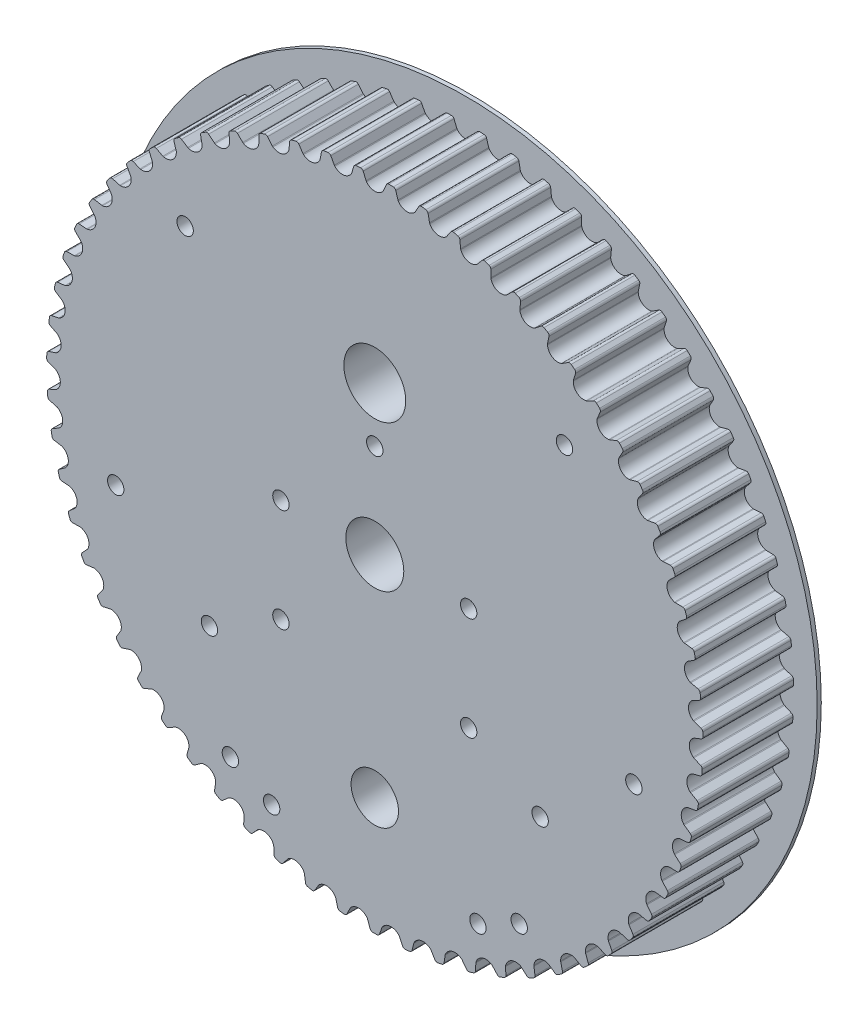
SolidWorks part; units mm, degrees
material "PETG"
ref_plane "Front Plane" through (0, 0, 0) normal (0, 0, 1) x (1, 0, 0)
ref_plane "Top Plane" through (0, 0, 0) normal (0, 1, 0) x (1, 0, 0)
ref_plane "Right Plane" through (0, 0, 0) normal (1, 0, 0) x (0, 0, -1)
sketch "Sketch1" plane through (0, 0, 0) normal (0, 0, 1) x (1, 0, 0)
  line L0 (0, 0) -> (0, 50000) construction
  line L1 (0, 0) -> (3.9983, 80.1144) construction
  line L2 (0, 0) -> (-3.9983, 80.1144) construction
  line L3 (-2.1085, 77.3973) -> (-2.8064, 79.0584)
  line L4 (2.1085, 77.3973) -> (2.8064, 79.0584)
  line L5 (5.6082, 77.2226) -> (5.0793, 78.9449)
  line L6 (9.8043, 76.8027) -> (10.6641, 78.3861)
  line L7 (13.2692, 76.2805) -> (12.9144, 78.0469)
  line L8 (17.4027, 75.4449) -> (18.4158, 76.9348)
  line L9 (20.7984, 74.5802) -> (20.6212, 76.3732)
  line L10 (24.8281, 73.3372) -> (25.9846, 74.7188)
  line L11 (28.1208, 72.1388) -> (28.123, 73.9405)
  line L12 (32.0068, 70.5007) -> (33.295, 71.7603)
  line L13 (35.1638, 68.9804) -> (35.3454, 70.7729)
  line L14 (38.8673, 66.9635) -> (40.2746, 68.0886)
  line L15 (41.8573, 65.1364) -> (42.2164, 66.902)
  line L16 (45.3416, 62.7608) -> (46.8539, 63.7402)
  line L17 (48.1348, 60.6451) -> (48.6679, 62.3661)
  line L18 (51.3652, 57.9344) -> (52.9675, 58.7583)
  line L19 (53.9339, 55.551) -> (54.6358, 57.2105)
  line L20 (56.8784, 52.5322) -> (58.5548, 53.1925)
  line L21 (59.197, 49.9049) -> (60.0606, 51.4862)
  line L22 (61.8263, 46.6079) -> (63.5601, 47.098)
  line L23 (63.8717, 43.7628) -> (64.8885, 45.2502)
  line L24 (66.1597, 40.2204) -> (67.9337, 40.5354)
  line L25 (67.9117, 37.1858) -> (69.0715, 38.5646)
  line L26 (69.8356, 33.4331) -> (71.6321, 33.57)
  line L27 (71.2767, 30.2392) -> (72.5681, 31.4956)
  line L28 (72.8174, 26.3136) -> (74.6186, 26.2709)
  line L29 (73.9334, 22.992) -> (75.3434, 24.1137)
  line L30 (75.0756, 18.9326) -> (76.8636, 18.7107)
  line L31 (75.8553, 15.5164) -> (77.37, 16.4921)
  line L32 (76.5876, 11.3634) -> (78.3446, 10.9646)
  line L33 (77.0233, 7.8865) -> (78.6276, 8.7066)
  line L34 (77.3384, 3.6813) -> (79.047, 3.1095)
  line L35 (77.4258, 0.1783) -> (79.1038, 0.8345)
  line L36 (77.3206, -4.0374) -> (78.9638, -4.7765)
  line L37 (77.0588, -7.5317) -> (78.7938, -7.0458)
  line L38 (76.5344, -11.716) -> (78.0959, -12.615)
  line L39 (75.9259, -15.1668) -> (77.7007, -14.8561)
  line L40 (74.9876, -19.2782) -> (76.4517, -20.3281)
  line L41 (74.0385, -22.6513) -> (75.8354, -22.5188)
  line L42 (72.6954, -26.6487) -> (74.0478, -27.8393)
  line L43 (71.4153, -29.9106) -> (73.2164, -29.9577)
  line L44 (69.6808, -33.7544) -> (70.908, -35.0737)
  line L45 (68.0823, -36.8726) -> (69.8697, -37.0988)
  line L46 (65.9737, -40.5247) -> (67.0634, -41.9596)
  line L47 (64.0726, -43.4682) -> (65.8287, -43.8712)
  line L48 (61.6109, -46.8922) -> (62.5523, -48.4284)
  line L49 (59.4262, -49.6317) -> (61.1334, -50.2076)
  line L50 (56.6358, -52.7936) -> (57.4196, -54.416)
  line L51 (54.1892, -55.302) -> (55.8306, -56.0451)
  line L52 (51.0978, -58.1704) -> (51.7161, -59.8627)
  line L53 (48.4136, -60.4227) -> (49.9728, -61.3255)
  line L54 (45.052, -62.969) -> (45.4988, -64.7145)
  line L55 (42.1568, -64.9429) -> (43.6185, -65.9965)
  line L56 (38.5585, -67.1418) -> (38.8292, -68.9231)
  line L57 (35.4811, -68.8177) -> (36.8306, -70.0115)
  line L58 (31.6817, -70.6474) -> (31.7737, -72.4468)
  line L59 (28.4528, -72.0085) -> (29.6767, -73.3307)
  line L60 (24.49, -73.4508) -> (24.4024, -75.2504)
  line L61 (21.1417, -74.4836) -> (22.2278, -75.9212)
  line L62 (17.055, -75.5242) -> (16.7887, -77.3062)
  line L63 (13.6204, -76.2185) -> (14.5581, -77.7571)
  line L64 (9.4505, -76.8471) -> (9.008, -78.5936)
  line L65 (5.9638, -77.1959) -> (6.7436, -78.8202)
  line L66 (1.752, -77.4061) -> (1.1379, -79.1)
  line L67 (-1.752, -77.4061) -> (-1.1379, -79.1)
  line L68 (-5.9638, -77.1959) -> (-6.7436, -78.8202)
  line L69 (-9.4505, -76.8471) -> (-9.008, -78.5936)
  line L70 (-13.6204, -76.2185) -> (-14.5581, -77.7571)
  line L71 (-17.055, -75.5242) -> (-16.7887, -77.3062)
  line L72 (-21.1417, -74.4836) -> (-22.2278, -75.9212)
  line L73 (-24.49, -73.4508) -> (-24.4024, -75.2504)
  line L74 (-28.4528, -72.0085) -> (-29.6767, -73.3307)
  line L75 (-31.6817, -70.6474) -> (-31.7737, -72.4468)
  line L76 (-35.4811, -68.8177) -> (-36.8306, -70.0115)
  line L77 (-38.5585, -67.1418) -> (-38.8292, -68.9231)
  line L78 (-42.1568, -64.9429) -> (-43.6185, -65.9965)
  line L79 (-45.052, -62.969) -> (-45.4988, -64.7145)
  line L80 (-48.4136, -60.4227) -> (-49.9728, -61.3255)
  line L81 (-51.0978, -58.1704) -> (-51.7161, -59.8627)
  line L82 (-54.1892, -55.302) -> (-55.8306, -56.0451)
  line L83 (-56.6358, -52.7936) -> (-57.4196, -54.416)
  line L84 (-59.4262, -49.6317) -> (-61.1334, -50.2076)
  line L85 (-61.6109, -46.8922) -> (-62.5523, -48.4284)
  line L86 (-64.0726, -43.4682) -> (-65.8287, -43.8712)
  line L87 (-65.9737, -40.5247) -> (-67.0634, -41.9596)
  line L88 (-68.0823, -36.8726) -> (-69.8697, -37.0988)
  line L89 (-69.6808, -33.7544) -> (-70.908, -35.0737)
  line L90 (-71.4153, -29.9106) -> (-73.2164, -29.9577)
  line L91 (-72.6954, -26.6487) -> (-74.0478, -27.8393)
  line L92 (-74.0385, -22.6513) -> (-75.8354, -22.5188)
  line L93 (-74.9876, -19.2782) -> (-76.4517, -20.3281)
  line L94 (-75.9259, -15.1668) -> (-77.7007, -14.8561)
  line L95 (-76.5344, -11.716) -> (-78.0959, -12.615)
  line L96 (-77.0588, -7.5317) -> (-78.7938, -7.0458)
  line L97 (-77.3206, -4.0374) -> (-78.9638, -4.7765)
  line L98 (-77.4258, 0.1783) -> (-79.1038, 0.8345)
  line L99 (-77.3384, 3.6813) -> (-79.047, 3.1095)
  line L100 (-77.0233, 7.8865) -> (-78.6276, 8.7066)
  line L101 (-76.5876, 11.3634) -> (-78.3446, 10.9646)
  line L102 (-75.8553, 15.5164) -> (-77.37, 16.4921)
  line L103 (-75.0756, 18.9326) -> (-76.8636, 18.7107)
  line L104 (-73.9334, 22.992) -> (-75.3434, 24.1137)
  line L105 (-72.8174, 26.3136) -> (-74.6186, 26.2709)
  line L106 (-71.2767, 30.2392) -> (-72.5681, 31.4956)
  line L107 (-69.8356, 33.4331) -> (-71.6321, 33.57)
  line L108 (-67.9117, 37.1858) -> (-69.0715, 38.5646)
  line L109 (-66.1597, 40.2204) -> (-67.9337, 40.5354)
  line L110 (-63.8717, 43.7628) -> (-64.8885, 45.2502)
  line L111 (-61.8263, 46.6079) -> (-63.5601, 47.098)
  line L112 (-59.197, 49.9049) -> (-60.0606, 51.4862)
  line L113 (-56.8784, 52.5322) -> (-58.5548, 53.1925)
  line L114 (-53.9339, 55.551) -> (-54.6358, 57.2105)
  line L115 (-51.3652, 57.9344) -> (-52.9675, 58.7583)
  line L116 (-48.1348, 60.6451) -> (-48.6679, 62.3661)
  line L117 (-45.3416, 62.7608) -> (-46.8539, 63.7402)
  line L118 (-41.8573, 65.1364) -> (-42.2164, 66.902)
  line L119 (-38.8673, 66.9635) -> (-40.2746, 68.0886)
  line L120 (-35.1638, 68.9804) -> (-35.3454, 70.7729)
  line L121 (-32.0068, 70.5007) -> (-33.295, 71.7603)
  line L122 (-28.1208, 72.1388) -> (-28.123, 73.9405)
  line L123 (0, 0) -> (2.0086, 77.226) construction
  line L124 (-24.8281, 73.3372) -> (-25.9846, 74.7188)
  line L125 (-20.7984, 74.5802) -> (-20.6212, 76.3732)
  line L126 (-17.4027, 75.4449) -> (-18.4158, 76.9348)
  line L127 (-13.2692, 76.2805) -> (-12.9144, 78.0469)
  line L128 (-9.8043, 76.8027) -> (-10.6641, 78.3861)
  line L129 (-5.6082, 77.2226) -> (-5.0793, 78.9449)
  circle A0 centre (0, 0) radius 80.2141 construction
  circle A317 centre (0, 0) radius 79.53 construction
  arc A318 (-2.0086, 77.226) -> (2.0086, 77.226) centre (0, 78.7807) ccw
  arc A319 (-2.0086, 77.226) -> (-2.1085, 77.3973) centre (-1.406, 77.6924) cw
  arc A320 (-2.8064, 79.0584) -> (-3.4334, 79.4559) centre (-3.4054, 78.8067) ccw
  arc A321 (-3.4334, 79.4559) -> (-3.9642, 79.4311) centre (0, 0) ccw
  arc A322 (3.4334, 79.4559) -> (3.9642, 79.4311) centre (0, 0) cw
  arc A323 (2.8064, 79.0584) -> (3.4334, 79.4559) centre (3.4054, 78.8067) cw
  arc A324 (2.0086, 77.226) -> (2.1085, 77.3973) centre (1.406, 77.6924) ccw
  arc A325 (4.4949, 79.4029) -> (3.9642, 79.4311) centre (0, 0) ccw
  arc A326 (5.0793, 78.9449) -> (4.4949, 79.4029) centre (4.4582, 78.7542) ccw
  arc A327 (5.6906, 77.0422) -> (9.6878, 76.6422) centre (7.844, 78.3892) ccw
  arc A328 (5.6906, 77.0422) -> (5.6082, 77.2226) centre (6.3366, 77.4463) cw
  arc A329 (9.6878, 76.6422) -> (9.8043, 76.8027) centre (9.1347, 77.1663) ccw
  arc A330 (10.6641, 78.3861) -> (11.3276, 78.7192) centre (11.2351, 78.0761) cw
  arc A331 (11.3276, 78.7192) -> (11.8533, 78.6417) centre (0, 0) cw
  arc A332 (12.3785, 78.5608) -> (11.8533, 78.6417) centre (0, 0) ccw
  arc A333 (12.9144, 78.0469) -> (12.3785, 78.5608) centre (12.2774, 77.919) ccw
  arc A334 (13.3333, 76.0928) -> (17.2708, 75.2968) centre (15.6101, 77.2187) ccw
  arc A335 (13.3333, 76.0928) -> (13.2692, 76.2805) centre (14.0163, 76.4305) cw
  arc A336 (17.2708, 75.2968) -> (17.4027, 75.4449) centre (16.7726, 75.8733) ccw
  arc A337 (18.4158, 76.9348) -> (19.1092, 77.2001) centre (18.9531, 76.5694) cw
  arc A338 (19.1092, 77.2001) -> (19.6246, 77.0707) centre (0, 0) cw
  arc A339 (20.1391, 76.9379) -> (19.6246, 77.0707) centre (0, 0) ccw
  arc A340 (20.6212, 76.3732) -> (20.1391, 76.9379) centre (19.9746, 76.3093) ccw
  arc A341 (20.8434, 74.3871) -> (24.6821, 73.203) centre (23.221, 75.2807) ccw
  arc A342 (20.8434, 74.3871) -> (20.7984, 74.5802) centre (21.5567, 74.6552) cw
  arc A343 (24.6821, 73.203) -> (24.8281, 73.3372) centre (24.2438, 73.8263) ccw
  arc A344 (25.9846, 74.7188) -> (26.7009, 74.9138) centre (26.4828, 74.3018) cw
  arc A345 (26.7009, 74.9138) -> (27.2009, 74.7338) centre (0, 0) cw
  arc A346 (27.6996, 74.5503) -> (27.2009, 74.7338) centre (0, 0) ccw
  arc A347 (28.123, 73.9405) -> (27.6996, 74.5503) centre (27.4733, 73.9413) ccw
  arc A348 (28.1464, 71.9421) -> (31.8481, 70.3817) centre (30.6012, 72.5945) ccw
  arc A349 (28.1464, 71.9421) -> (28.1208, 72.1388) centre (28.8828, 72.1378) cw
  arc A350 (31.8481, 70.3817) -> (32.0068, 70.5007) centre (31.474, 71.0455) ccw
  arc A351 (33.295, 71.7603) -> (34.0272, 71.883) centre (33.7493, 71.2958) cw
  arc A352 (34.0272, 71.883) -> (34.5068, 71.6541) centre (0, 0) cw
  arc A353 (34.9848, 71.4219) -> (34.5068, 71.6541) centre (0, 0) ccw
  arc A354 (35.3454, 70.7729) -> (34.9848, 71.4219) centre (34.699, 70.8384) ccw
  arc A355 (35.1696, 68.7821) -> (38.6976, 66.8609) centre (37.6772, 69.1869) ccw
  arc A356 (35.1696, 68.7821) -> (35.1638, 68.9804) centre (35.9219, 68.9036) cw
  arc A357 (38.6976, 66.8609) -> (38.8673, 66.9635) centre (38.3915, 67.5587) ccw
  arc A358 (40.2746, 68.0886) -> (41.0154, 68.1378) centre (40.6803, 67.5811) cw
  arc A359 (41.0154, 68.1378) -> (41.4697, 67.8622) centre (0, 0) cw
  arc A360 (41.9222, 67.5836) -> (41.4697, 67.8622) centre (0, 0) ccw
  arc A361 (42.2164, 66.902) -> (41.9222, 67.5836) centre (41.5798, 67.0315) ccw
  arc A362 (41.8434, 64.9386) -> (45.1625, 62.6756) centre (44.3787, 65.0917) ccw
  arc A363 (41.8434, 64.9386) -> (41.8573, 65.1364) centre (42.604, 64.9845) cw
  arc A364 (45.1625, 62.6756) -> (45.3416, 62.7608) centre (44.9274, 63.4004) ccw
  arc A365 (46.8539, 63.7402) -> (47.5959, 63.7154) centre (47.2071, 63.1949) cw
  arc A366 (47.5959, 63.7154) -> (48.0206, 63.3959) centre (0, 0) cw
  arc A367 (48.4431, 63.0737) -> (48.0206, 63.3959) centre (0, 0) ccw
  arc A368 (48.6679, 62.3661) -> (48.4431, 63.0737) centre (48.0473, 62.5584) ccw
  arc A369 (48.1012, 60.4496) -> (51.1786, 57.8674) centre (50.6393, 60.3495) ccw
  arc A370 (48.1012, 60.4496) -> (48.1348, 60.6451) centre (48.8626, 60.4196) cw
  arc A371 (51.1786, 57.8674) -> (51.3652, 57.9344) centre (51.0168, 58.6121) ccw
  arc A372 (52.9675, 58.7583) -> (53.7034, 58.6597) centre (53.2647, 58.1805) cw
  arc A373 (53.7034, 58.6597) -> (54.0941, 58.2996) centre (0, 0) cw
  arc A374 (54.4825, 57.9369) -> (54.0941, 58.2996) centre (0, 0) ccw
  arc A375 (54.6358, 57.2105) -> (54.4825, 57.9369) centre (54.0374, 57.4636) ccw
  arc A376 (53.881, 55.3599) -> (56.686, 52.4841) centre (56.3965, 55.0076) ccw
  arc A377 (53.881, 55.3599) -> (53.9339, 55.551) centre (54.6357, 55.2542) cw
  arc A378 (56.686, 52.4841) -> (56.8784, 52.5322) centre (56.5991, 53.2412) ccw
  arc A379 (58.5548, 53.1925) -> (59.2772, 53.0211) centre (58.7929, 52.588) cw
  arc A380 (59.2772, 53.0211) -> (59.6301, 52.6239) centre (0, 0) cw
  arc A381 (59.9804, 52.2243) -> (59.6301, 52.6239) centre (0, 0) ccw
  arc A382 (60.0606, 51.4862) -> (59.9804, 52.2243) centre (59.4904, 51.7976) ccw
  arc A383 (59.1254, 49.72) -> (61.63, 46.5792) centre (61.5932, 49.119) ccw
  arc A384 (59.1254, 49.72) -> (59.197, 49.9049) centre (59.8657, 49.5397) cw
  arc A385 (61.63, 46.5792) -> (61.8263, 46.6079) centre (61.619, 47.3411) ccw
  arc A386 (63.5601, 47.098) -> (64.2618, 46.8555) centre (63.7368, 46.4728) cw
  arc A387 (64.2618, 46.8555) -> (64.5734, 46.4251) centre (0, 0) cw
  arc A388 (64.8822, 45.9926) -> (64.5734, 46.4251) centre (0, 0) ccw
  arc A389 (64.8885, 45.2502) -> (64.8822, 45.9926) centre (64.3521, 45.6169) ccw
  arc A390 (63.7821, 43.5859) -> (65.9616, 40.2114) centre (66.1778, 42.7422) ccw
  arc A391 (63.7821, 43.5859) -> (63.8717, 43.7628) centre (64.5008, 43.3328) cw
  arc A392 (65.9616, 40.2114) -> (66.1597, 40.2204) centre (66.0264, 40.9706) ccw
  arc A393 (67.9337, 40.5354) -> (68.6078, 40.2243) centre (68.0473, 39.8957) cw
  arc A394 (68.6078, 40.2243) -> (68.875, 39.765) centre (0, 0) cw
  arc A395 (69.1392, 39.3039) -> (68.875, 39.765) centre (0, 0) ccw
  arc A396 (69.0715, 38.5646) -> (69.1392, 39.3039) centre (68.5743, 38.9828) ccw
  arc A397 (67.8049, 37.0187) -> (69.6375, 33.4439) centre (70.1047, 35.9406) ccw
  arc A398 (67.8049, 37.0187) -> (67.9117, 37.1858) centre (68.4948, 36.6953) cw
  arc A399 (69.6375, 33.4439) -> (69.8356, 33.4331) centre (69.7777, 34.1929) ccw
  arc A400 (71.6321, 33.57) -> (72.2719, 33.1933) centre (71.6815, 32.9221) cw
  arc A401 (72.2719, 33.1933) -> (72.4921, 32.7097) centre (0, 0) cw
  arc A402 (72.709, 32.2246) -> (72.4921, 32.7097) centre (0, 0) ccw
  arc A403 (72.5681, 31.4956) -> (72.709, 32.2246) centre (72.115, 31.9613) ccw
  arc A404 (71.1538, 30.0836) -> (72.6214, 26.3441) centre (73.3349, 28.7818) ccw
  arc A405 (71.1538, 30.0836) -> (71.2767, 30.2392) centre (71.8081, 29.693) cw
  arc A406 (72.6214, 26.3441) -> (72.8174, 26.3136) centre (72.8355, 27.0754) ccw
  arc A407 (74.6186, 26.2709) -> (75.2177, 25.8324) centre (74.6032, 25.6214) cw
  arc A408 (75.2177, 25.8324) -> (75.3887, 25.3292) centre (0, 0) cw
  arc A409 (75.5562, 24.825) -> (75.3887, 25.3292) centre (0, 0) ccw
  arc A410 (75.3434, 24.1137) -> (75.5562, 24.825) centre (74.939, 24.6222) ccw
  arc A411 (73.7956, 22.8494) -> (74.8836, 18.9824) centre (75.8362, 21.337) ccw
  arc A412 (73.7956, 22.8494) -> (73.9334, 22.992) centre (74.4078, 22.3957) cw
  arc A413 (74.8836, 18.9824) -> (75.0756, 18.9326) centre (75.1694, 19.6888) ccw
  arc A414 (76.8636, 18.7107) -> (77.416, 18.2148) centre (76.7836, 18.066) cw
  arc A415 (77.416, 18.2148) -> (77.536, 17.6971) centre (0, 0) cw
  arc A416 (77.6525, 17.1786) -> (77.536, 17.6971) centre (0, 0) ccw
  arc A417 (77.37, 16.4921) -> (77.6525, 17.1786) centre (77.0181, 17.0383) ccw
  arc A418 (75.7039, 15.3882) -> (76.4015, 11.4321) centre (77.5838, 13.6801) ccw
  arc A419 (75.7039, 15.3882) -> (75.8553, 15.5164) centre (76.2679, 14.8758) cw
  arc A420 (76.4015, 11.4321) -> (76.5876, 11.3634) centre (76.7562, 12.1065) ccw
  arc A421 (78.3446, 10.9646) -> (78.8449, 10.4161) centre (78.2008, 10.331) cw
  arc A422 (78.8449, 10.4161) -> (78.9128, 9.8891) centre (0, 0) cw
  arc A423 (78.9771, 9.3616) -> (78.9128, 9.8891) centre (0, 0) ccw
  arc A424 (78.6276, 8.7066) -> (78.9771, 9.3616) centre (78.3319, 9.2851) ccw
  arc A425 (76.8599, 7.7741) -> (77.1601, 3.7681) centre (78.5604, 5.8873) ccw
  arc A426 (76.8599, 7.7741) -> (77.0233, 7.8865) centre (77.3701, 7.208) cw
  arc A427 (77.1601, 3.7681) -> (77.3384, 3.6813) centre (77.5802, 4.4039) ccw
  arc A428 (79.047, 3.1095) -> (79.4903, 2.5139) centre (78.8409, 2.4934) cw
  arc A429 (79.4903, 2.5139) -> (79.5053, 1.9827) centre (0, 0) cw
  arc A430 (79.5168, 1.4515) -> (79.5053, 1.9827) centre (0, 0) ccw
  arc A431 (79.1038, 0.8345) -> (79.5168, 1.4515) centre (78.8671, 1.4396) ccw
  arc A432 (77.252, 0.0827) -> (77.1519, -3.9333) centre (78.7562, -1.9641) ccw
  arc A433 (77.252, 0.0827) -> (77.4258, 0.1783) centre (77.7033, -0.5314) cw
  arc A434 (77.1519, -3.9333) -> (77.3206, -4.0374) centre (77.6332, -3.3425) ccw
  arc A435 (78.9638, -4.7765) -> (79.3456, -5.4133) centre (78.6973, -5.369) cw
  arc A436 (79.3456, -5.4133) -> (79.3076, -5.9433) centre (0, 0) cw
  arc A437 (79.2661, -6.4731) -> (79.3076, -5.9433) centre (0, 0) ccw
  arc A438 (78.7938, -7.0458) -> (79.2661, -6.4731) centre (78.6186, -6.4202) ccw
  arc A439 (76.8764, -7.6096) -> (76.3769, -11.5956) centre (78.1693, -9.7959) ccw
  arc A440 (76.8764, -7.6096) -> (77.0588, -7.5317) centre (77.2643, -8.2655) cw
  arc A441 (76.3769, -11.5956) -> (76.5344, -11.716) centre (76.9146, -11.0557) ccw
  arc A442 (78.0959, -12.615) -> (78.4123, -13.2866) centre (77.7717, -13.1781) cw
  arc A443 (78.4123, -13.2866) -> (78.3218, -13.8102) centre (0, 0) cw
  arc A444 (78.2277, -14.3332) -> (78.3218, -13.8102) centre (0, 0) ccw
  arc A445 (77.7007, -14.8561) -> (78.2277, -14.3332) centre (77.5887, -14.2161) ccw
  arc A446 (75.7367, -15.2262) -> (74.8428, -19.1426) centre (76.8055, -17.5304) ccw
  arc A447 (75.7367, -15.2262) -> (75.9259, -15.1668) centre (76.0573, -15.9174) cw
  arc A448 (74.8428, -19.1426) -> (74.9876, -19.2782) centre (75.4316, -18.6589) ccw
  arc A449 (76.4517, -20.3281) -> (76.6997, -21.0279) centre (76.0731, -20.8561) cw
  arc A450 (76.6997, -21.0279) -> (76.5575, -21.5399) centre (0, 0) cw
  arc A451 (76.4119, -22.051) -> (76.5575, -21.5399) centre (0, 0) ccw
  arc A452 (75.8354, -22.5188) -> (76.4119, -22.051) centre (75.7876, -21.8708) ccw
  arc A453 (73.8443, -22.6914) -> (72.5649, -26.4994) centre (74.6784, -25.0906) ccw
  arc A454 (73.8443, -22.6914) -> (74.0385, -22.6513) centre (74.0945, -23.4112) cw
  arc A455 (72.5649, -26.4994) -> (72.6954, -26.6487) centre (73.1989, -26.0768) ccw
  arc A456 (74.0478, -27.8393) -> (74.2249, -28.5603) centre (73.6185, -28.3269) cw
  arc A457 (74.2249, -28.5603) -> (74.0324, -29.0556) centre (0, 0) cw
  arc A458 (73.8366, -29.5496) -> (74.0324, -29.0556) centre (0, 0) ccw
  arc A459 (73.2164, -29.9577) -> (73.8366, -29.5496) centre (73.2334, -29.3082) ccw
  arc A460 (71.218, -29.9312) -> (69.5658, -33.5929) centre (71.8091, -32.4015) ccw
  arc A461 (71.218, -29.9312) -> (71.4153, -29.9106) centre (71.3953, -30.6723) cw
  arc A462 (69.5658, -33.5929) -> (69.6808, -33.7544) centre (70.2388, -33.2355) ccw
  arc A463 (70.908, -35.0737) -> (71.0123, -35.8088) centre (70.4322, -35.5162) cw
  arc A464 (71.0123, -35.8088) -> (70.7715, -36.2824) centre (0, 0) cw
  arc A465 (70.5275, -36.7545) -> (70.7715, -36.2824) centre (0, 0) ccw
  arc A466 (69.8697, -37.0988) -> (70.5275, -36.7545) centre (69.9513, -36.4542) ccw
  arc A467 (67.8839, -36.8735) -> (65.8754, -40.3525) centre (68.2261, -39.3903) ccw
  arc A468 (67.8839, -36.8735) -> (68.0823, -36.8726) centre (67.9866, -37.6286) cw
  arc A469 (65.8754, -40.3525) -> (65.9737, -40.5247) centre (66.5806, -40.0638) ccw
  arc A470 (67.0634, -41.9596) -> (67.0941, -42.7014) centre (66.5459, -42.3525) cw
  arc A471 (67.0941, -42.7014) -> (66.8073, -43.1487) centre (0, 0) cw
  arc A472 (66.5175, -43.5941) -> (66.8073, -43.1487) centre (0, 0) ccw
  arc A473 (65.8287, -43.8712) -> (66.5175, -43.5941) centre (65.974, -43.238) ccw
  arc A474 (63.8752, -43.4493) -> (61.5302, -46.711) centre (63.965, -45.9877) ccw
  arc A475 (63.8752, -43.4493) -> (64.0726, -43.4682) centre (63.9021, -44.2108) cw
  arc A476 (61.5302, -46.711) -> (61.6109, -46.8922) centre (62.2607, -46.494) ccw
  arc A477 (62.5523, -48.4284) -> (62.509, -49.1696) centre (61.9983, -48.7679) cw
  arc A478 (62.509, -49.1696) -> (62.1791, -49.5861) centre (0, 0) cw
  arc A479 (61.8464, -50.0005) -> (62.1791, -49.5861) centre (0, 0) ccw
  arc A480 (61.1334, -50.2076) -> (61.8464, -50.0005) centre (61.3411, -49.592) ccw
  arc A481 (59.2316, -49.5933) -> (56.5735, -52.6053) centre (59.0683, -52.1281) ccw
  arc A482 (59.2316, -49.5933) -> (59.4262, -49.6317) centre (59.1826, -50.3538) cw
  arc A483 (56.5735, -52.6053) -> (56.6358, -52.7936) centre (57.322, -52.4621) ccw
  arc A484 (57.4196, -54.416) -> (57.3027, -55.1491) centre (56.8345, -54.6986) cw
  arc A485 (57.3027, -55.1491) -> (56.9329, -55.5308) centre (0, 0) cw
  arc A486 (56.5606, -55.9099) -> (56.9329, -55.5308) centre (0, 0) ccw
  arc A487 (55.8306, -56.0451) -> (56.5606, -55.9099) centre (56.0985, -55.4532) ccw
  arc A488 (53.9994, -55.2445) -> (51.0546, -57.9768) centre (53.5845, -57.7503) ccw
  arc A489 (53.9994, -55.2445) -> (54.1892, -55.302) centre (53.8749, -55.9962) cw
  arc A490 (51.0546, -57.9768) -> (51.0978, -58.1704) centre (51.8136, -57.9089) ccw
  arc A491 (51.7161, -59.8627) -> (51.5268, -60.5806) centre (51.1059, -60.0857) cw
  arc A492 (51.5268, -60.5806) -> (51.1209, -60.9235) centre (0, 0) cw
  arc A493 (50.7127, -61.2637) -> (51.1209, -60.9235) centre (0, 0) ccw
  arc A494 (49.9728, -61.3255) -> (50.7127, -61.2637) centre (50.2984, -60.7632) ccw
  arc A495 (48.2305, -60.3465) -> (45.0283, -62.7721) centre (47.5681, -62.7987) ccw
  arc A496 (48.2305, -60.3465) -> (48.4136, -60.4227) centre (48.0318, -61.0822) cw
  arc A497 (45.0283, -62.7721) -> (45.052, -62.969) centre (45.7902, -62.7801) ccw
  arc A498 (45.4988, -64.7145) -> (45.2389, -65.41) centre (44.8693, -64.8756) cw
  arc A499 (45.2389, -65.41) -> (44.8008, -65.7108) centre (0, 0) cw
  arc A500 (44.3608, -66.0086) -> (44.8008, -65.7108) centre (0, 0) ccw
  arc A501 (43.6185, -65.9965) -> (44.3608, -66.0086) centre (43.9984, -65.4694) ccw
  arc A502 (41.9822, -64.8489) -> (38.5544, -66.9436) centre (41.079, -67.2229) ccw
  arc A503 (41.9822, -64.8489) -> (42.1568, -64.9429) centre (41.7113, -65.5611) cw
  arc A504 (38.5544, -66.9436) -> (38.5585, -67.1418) centre (39.3118, -67.0273) ccw
  arc A505 (38.8292, -68.9231) -> (38.5014, -69.5893) centre (38.1868, -69.0208) cw
  arc A506 (38.5014, -69.5893) -> (38.0355, -69.845) centre (0, 0) cw
  arc A507 (37.568, -70.0975) -> (38.0355, -69.845) centre (0, 0) ccw
  arc A508 (36.8306, -70.0115) -> (37.568, -70.0975) centre (37.2611, -69.5249) ccw
  arc A509 (35.3168, -68.7067) -> (31.6974, -70.4497) centre (34.1817, -70.979) ccw
  arc A510 (35.3168, -68.7067) -> (35.4811, -68.8177) centre (34.9762, -69.3884) cw
  arc A511 (31.6974, -70.4497) -> (31.6817, -70.6474) centre (32.4427, -70.6085) ccw
  arc A512 (31.7737, -72.4468) -> (31.3812, -73.077) centre (31.1248, -72.48) cw
  arc A513 (31.3812, -73.077) -> (30.8922, -73.285) centre (0, 0) cw
  arc A514 (30.4019, -73.4898) -> (30.8922, -73.285) centre (0, 0) ccw
  arc A515 (29.6767, -73.3307) -> (30.4019, -73.4898) centre (30.1535, -72.8894) ccw
  arc A516 (28.3003, -71.8817) -> (24.5254, -73.2556) centre (26.9446, -74.0296) ccw
  arc A517 (28.3003, -71.8817) -> (28.4528, -72.0085) centre (27.8936, -72.5261) cw
  arc A518 (24.5254, -73.2556) -> (24.49, -73.4508) centre (25.2511, -73.4878) ccw
  arc A519 (24.4024, -75.2504) -> (23.9491, -75.8384) centre (23.7535, -75.2188) cw
  arc A520 (23.9491, -75.8384) -> (23.4419, -75.9967) centre (0, 0) cw
  arc A521 (22.9336, -76.1516) -> (23.4419, -75.9967) centre (0, 0) ccw
  arc A522 (22.2278, -75.9212) -> (22.9336, -76.1516) centre (22.7462, -75.5295) ccw
  arc A523 (21.0026, -74.3423) -> (17.1096, -75.3336) centre (19.4397, -76.3446) ccw
  arc A524 (21.0026, -74.3423) -> (21.1417, -74.4836) centre (20.5337, -74.943) cw
  arc A525 (17.1096, -75.3336) -> (17.055, -75.5242) centre (17.8086, -75.6369) ccw
  arc A526 (16.7887, -77.3062) -> (16.2791, -77.8461) centre (16.1461, -77.2101) cw
  arc A527 (16.2791, -77.8461) -> (15.7586, -77.9531) centre (0, 0) cw
  arc A528 (15.2374, -78.0567) -> (15.7586, -77.9531) centre (0, 0) ccw
  arc A529 (14.5581, -77.7571) -> (15.2374, -78.0567) centre (15.1129, -77.419) ccw
  arc A530 (13.4961, -76.0641) -> (9.5238, -76.6628) centre (11.7417, -77.9008) ccw
  arc A531 (13.4961, -76.0641) -> (13.6204, -76.2185) centre (12.9698, -76.6151) cw
  arc A532 (9.5238, -76.6628) -> (9.4505, -76.8471) centre (10.1891, -77.0342) ccw
  arc A533 (9.008, -78.5936) -> (8.4472, -79.0801) centre (8.3782, -78.4341) cw
  arc A534 (8.4472, -79.0801) -> (7.9186, -79.1348) centre (0, 0) cw
  arc A535 (7.3897, -79.1859) -> (7.9186, -79.1348) centre (0, 0) ccw
  arc A536 (6.7436, -78.8202) -> (7.3897, -79.1859) centre (7.3293, -78.539) ccw
  arc A537 (5.8555, -77.0298) -> (1.8433, -77.2301) centre (3.9269, -78.6828) ccw
  arc A538 (5.8555, -77.0298) -> (5.9638, -77.1959) centre (5.2769, -77.5257) cw
  arc A539 (1.8433, -77.2301) -> (1.752, -77.4061) centre (2.4684, -77.6659) ccw
  arc A540 (1.1379, -79.1) -> (0.5314, -79.5282) centre (0.527, -78.8785) cw
  arc A541 (0.5314, -79.5282) -> (0, -79.53) centre (0, 0) cw
  arc A542 (-0.5314, -79.5282) -> (0, -79.53) centre (0, 0) ccw
  arc A543 (-1.1379, -79.1) -> (-0.5314, -79.5282) centre (-0.527, -78.8785) ccw
  arc A544 (-1.8433, -77.2301) -> (-5.8555, -77.0298) centre (-3.9269, -78.6828) ccw
  arc A545 (-1.8433, -77.2301) -> (-1.752, -77.4061) centre (-2.4684, -77.6659) cw
  arc A546 (-5.8555, -77.0298) -> (-5.9638, -77.1959) centre (-5.2769, -77.5257) ccw
  arc A547 (-6.7436, -78.8202) -> (-7.3897, -79.1859) centre (-7.3293, -78.539) cw
  arc A548 (-7.3897, -79.1859) -> (-7.9186, -79.1348) centre (0, 0) cw
  arc A549 (-8.4472, -79.0801) -> (-7.9186, -79.1348) centre (0, 0) ccw
  arc A550 (-9.008, -78.5936) -> (-8.4472, -79.0801) centre (-8.3782, -78.4341) ccw
  arc A551 (-9.5238, -76.6628) -> (-13.4961, -76.0641) centre (-11.7417, -77.9008) ccw
  arc A552 (-9.5238, -76.6628) -> (-9.4505, -76.8471) centre (-10.1891, -77.0342) cw
  arc A553 (-13.4961, -76.0641) -> (-13.6204, -76.2185) centre (-12.9698, -76.6151) ccw
  arc A554 (-14.5581, -77.7571) -> (-15.2374, -78.0567) centre (-15.1129, -77.419) cw
  arc A555 (-15.2374, -78.0567) -> (-15.7586, -77.9531) centre (0, 0) cw
  arc A556 (-16.2791, -77.8461) -> (-15.7586, -77.9531) centre (0, 0) ccw
  arc A557 (-16.7887, -77.3062) -> (-16.2791, -77.8461) centre (-16.1461, -77.2101) ccw
  arc A558 (-17.1096, -75.3336) -> (-21.0026, -74.3423) centre (-19.4397, -76.3446) ccw
  arc A559 (-17.1096, -75.3336) -> (-17.055, -75.5242) centre (-17.8086, -75.6369) cw
  arc A560 (-21.0026, -74.3423) -> (-21.1417, -74.4836) centre (-20.5337, -74.943) ccw
  arc A561 (-22.2278, -75.9212) -> (-22.9336, -76.1516) centre (-22.7462, -75.5295) cw
  arc A562 (-22.9336, -76.1516) -> (-23.4419, -75.9967) centre (0, 0) cw
  arc A563 (-23.9491, -75.8384) -> (-23.4419, -75.9967) centre (0, 0) ccw
  arc A564 (-24.4024, -75.2504) -> (-23.9491, -75.8384) centre (-23.7535, -75.2188) ccw
  arc A565 (-24.5254, -73.2556) -> (-28.3003, -71.8817) centre (-26.9446, -74.0296) ccw
  arc A566 (-24.5254, -73.2556) -> (-24.49, -73.4508) centre (-25.2511, -73.4878) cw
  arc A567 (-28.3003, -71.8817) -> (-28.4528, -72.0085) centre (-27.8936, -72.5261) ccw
  arc A568 (-29.6767, -73.3307) -> (-30.4019, -73.4898) centre (-30.1535, -72.8894) cw
  arc A569 (-30.4019, -73.4898) -> (-30.8922, -73.285) centre (0, 0) cw
  arc A570 (-31.3812, -73.077) -> (-30.8922, -73.285) centre (0, 0) ccw
  arc A571 (-31.7737, -72.4468) -> (-31.3812, -73.077) centre (-31.1248, -72.48) ccw
  arc A572 (-31.6974, -70.4497) -> (-35.3168, -68.7067) centre (-34.1817, -70.979) ccw
  arc A573 (-31.6974, -70.4497) -> (-31.6817, -70.6474) centre (-32.4427, -70.6085) cw
  arc A574 (-35.3168, -68.7067) -> (-35.4811, -68.8177) centre (-34.9762, -69.3884) ccw
  arc A575 (-36.8306, -70.0115) -> (-37.568, -70.0975) centre (-37.2611, -69.5249) cw
  arc A576 (-37.568, -70.0975) -> (-38.0355, -69.845) centre (0, 0) cw
  arc A577 (-38.5014, -69.5893) -> (-38.0355, -69.845) centre (0, 0) ccw
  arc A578 (-38.8292, -68.9231) -> (-38.5014, -69.5893) centre (-38.1868, -69.0208) ccw
  arc A579 (-38.5544, -66.9436) -> (-41.9822, -64.8489) centre (-41.079, -67.2229) ccw
  arc A580 (-38.5544, -66.9436) -> (-38.5585, -67.1418) centre (-39.3118, -67.0273) cw
  arc A581 (-41.9822, -64.8489) -> (-42.1568, -64.9429) centre (-41.7113, -65.5611) ccw
  arc A582 (-43.6185, -65.9965) -> (-44.3608, -66.0086) centre (-43.9984, -65.4694) cw
  arc A583 (-44.3608, -66.0086) -> (-44.8008, -65.7108) centre (0, 0) cw
  arc A584 (-45.2389, -65.41) -> (-44.8008, -65.7108) centre (0, 0) ccw
  arc A585 (-45.4988, -64.7145) -> (-45.2389, -65.41) centre (-44.8693, -64.8756) ccw
  arc A586 (-45.0283, -62.7721) -> (-48.2305, -60.3465) centre (-47.5681, -62.7987) ccw
  arc A587 (-45.0283, -62.7721) -> (-45.052, -62.969) centre (-45.7902, -62.7801) cw
  arc A588 (-48.2305, -60.3465) -> (-48.4136, -60.4227) centre (-48.0318, -61.0822) ccw
  arc A589 (-49.9728, -61.3255) -> (-50.7127, -61.2637) centre (-50.2984, -60.7632) cw
  arc A590 (-50.7127, -61.2637) -> (-51.1209, -60.9235) centre (0, 0) cw
  arc A591 (-51.5268, -60.5806) -> (-51.1209, -60.9235) centre (0, 0) ccw
  arc A592 (-51.7161, -59.8627) -> (-51.5268, -60.5806) centre (-51.1059, -60.0857) ccw
  arc A593 (-51.0546, -57.9768) -> (-53.9994, -55.2445) centre (-53.5845, -57.7503) ccw
  arc A594 (-51.0546, -57.9768) -> (-51.0978, -58.1704) centre (-51.8136, -57.9089) cw
  arc A595 (-53.9994, -55.2445) -> (-54.1892, -55.302) centre (-53.8749, -55.9962) ccw
  arc A596 (-55.8306, -56.0451) -> (-56.5606, -55.9099) centre (-56.0985, -55.4532) cw
  arc A597 (-56.5606, -55.9099) -> (-56.9329, -55.5308) centre (0, 0) cw
  arc A598 (-57.3027, -55.1491) -> (-56.9329, -55.5308) centre (0, 0) ccw
  arc A599 (-57.4196, -54.416) -> (-57.3027, -55.1491) centre (-56.8345, -54.6986) ccw
  arc A600 (-56.5735, -52.6053) -> (-59.2316, -49.5933) centre (-59.0683, -52.1281) ccw
  arc A601 (-56.5735, -52.6053) -> (-56.6358, -52.7936) centre (-57.322, -52.4621) cw
  arc A602 (-59.2316, -49.5933) -> (-59.4262, -49.6317) centre (-59.1826, -50.3538) ccw
  arc A603 (-61.1334, -50.2076) -> (-61.8464, -50.0005) centre (-61.3411, -49.592) cw
  arc A604 (-61.8464, -50.0005) -> (-62.1791, -49.5861) centre (0, 0) cw
  arc A605 (-62.509, -49.1696) -> (-62.1791, -49.5861) centre (0, 0) ccw
  arc A606 (-62.5523, -48.4284) -> (-62.509, -49.1696) centre (-61.9983, -48.7679) ccw
  arc A607 (-61.5302, -46.711) -> (-63.8752, -43.4493) centre (-63.965, -45.9877) ccw
  arc A608 (-61.5302, -46.711) -> (-61.6109, -46.8922) centre (-62.2607, -46.494) cw
  arc A609 (-63.8752, -43.4493) -> (-64.0726, -43.4682) centre (-63.9021, -44.2108) ccw
  arc A610 (-65.8287, -43.8712) -> (-66.5175, -43.5941) centre (-65.974, -43.238) cw
  arc A611 (-66.5175, -43.5941) -> (-66.8073, -43.1487) centre (0, 0) cw
  arc A612 (-67.0941, -42.7014) -> (-66.8073, -43.1487) centre (0, 0) ccw
  arc A613 (-67.0634, -41.9596) -> (-67.0941, -42.7014) centre (-66.5459, -42.3525) ccw
  arc A614 (-65.8754, -40.3525) -> (-67.8839, -36.8735) centre (-68.2261, -39.3904) ccw
  arc A615 (-65.8754, -40.3525) -> (-65.9737, -40.5247) centre (-66.5806, -40.0638) cw
  arc A616 (-67.8839, -36.8735) -> (-68.0823, -36.8726) centre (-67.9866, -37.6286) ccw
  arc A617 (-69.8697, -37.0988) -> (-70.5275, -36.7545) centre (-69.9513, -36.4542) cw
  arc A618 (-70.5275, -36.7545) -> (-70.7715, -36.2824) centre (0, 0) cw
  arc A619 (-71.0123, -35.8088) -> (-70.7715, -36.2824) centre (0, 0) ccw
  arc A620 (-70.908, -35.0737) -> (-71.0123, -35.8088) centre (-70.4322, -35.5162) ccw
  arc A621 (-69.5658, -33.5929) -> (-71.218, -29.9312) centre (-71.8091, -32.4015) ccw
  arc A622 (-69.5658, -33.5929) -> (-69.6808, -33.7544) centre (-70.2388, -33.2355) cw
  arc A623 (-71.218, -29.9312) -> (-71.4153, -29.9106) centre (-71.3953, -30.6723) ccw
  arc A624 (-73.2164, -29.9577) -> (-73.8366, -29.5496) centre (-73.2334, -29.3082) cw
  arc A625 (-73.8366, -29.5496) -> (-74.0324, -29.0556) centre (0, 0) cw
  arc A626 (-74.2249, -28.5603) -> (-74.0324, -29.0556) centre (0, 0) ccw
  arc A627 (-74.0478, -27.8393) -> (-74.2249, -28.5603) centre (-73.6185, -28.3269) ccw
  arc A628 (-72.5649, -26.4994) -> (-73.8443, -22.6914) centre (-74.6784, -25.0906) ccw
  arc A629 (-72.5649, -26.4994) -> (-72.6954, -26.6487) centre (-73.1989, -26.0768) cw
  arc A630 (-73.8443, -22.6914) -> (-74.0385, -22.6513) centre (-74.0945, -23.4112) ccw
  arc A631 (-75.8354, -22.5188) -> (-76.4119, -22.051) centre (-75.7876, -21.8708) cw
  arc A632 (-76.4119, -22.051) -> (-76.5575, -21.5399) centre (0, 0) cw
  arc A633 (-76.6997, -21.0279) -> (-76.5575, -21.5399) centre (0, 0) ccw
  arc A634 (-76.4517, -20.3281) -> (-76.6997, -21.0279) centre (-76.0731, -20.8561) ccw
  arc A635 (-74.8428, -19.1426) -> (-75.7367, -15.2262) centre (-76.8055, -17.5304) ccw
  arc A636 (-74.8428, -19.1426) -> (-74.9876, -19.2782) centre (-75.4316, -18.6589) cw
  arc A637 (-75.7367, -15.2262) -> (-75.9259, -15.1668) centre (-76.0573, -15.9174) ccw
  arc A638 (-77.7007, -14.8561) -> (-78.2277, -14.3332) centre (-77.5887, -14.2161) cw
  arc A639 (-78.2277, -14.3332) -> (-78.3218, -13.8102) centre (0, 0) cw
  arc A640 (-78.4123, -13.2866) -> (-78.3218, -13.8102) centre (0, 0) ccw
  arc A641 (-78.0959, -12.615) -> (-78.4123, -13.2866) centre (-77.7717, -13.1781) ccw
  arc A642 (-76.3769, -11.5956) -> (-76.8764, -7.6096) centre (-78.1693, -9.7959) ccw
  arc A643 (-76.3769, -11.5956) -> (-76.5344, -11.716) centre (-76.9146, -11.0557) cw
  arc A644 (-76.8764, -7.6096) -> (-77.0588, -7.5317) centre (-77.2643, -8.2655) ccw
  arc A645 (-78.7938, -7.0458) -> (-79.2661, -6.4731) centre (-78.6186, -6.4202) cw
  arc A646 (-79.2661, -6.4731) -> (-79.3076, -5.9433) centre (0, 0) cw
  arc A647 (-79.3456, -5.4133) -> (-79.3076, -5.9433) centre (0, 0) ccw
  arc A648 (-78.9638, -4.7765) -> (-79.3456, -5.4133) centre (-78.6973, -5.369) ccw
  arc A649 (-77.1519, -3.9333) -> (-77.252, 0.0827) centre (-78.7562, -1.9641) ccw
  arc A650 (-77.1519, -3.9333) -> (-77.3206, -4.0374) centre (-77.6332, -3.3425) cw
  arc A651 (-77.252, 0.0827) -> (-77.4258, 0.1783) centre (-77.7033, -0.5314) ccw
  arc A652 (-79.1038, 0.8345) -> (-79.5168, 1.4515) centre (-78.8671, 1.4396) cw
  arc A653 (-79.5168, 1.4515) -> (-79.5053, 1.9827) centre (0, 0) cw
  arc A654 (-79.4903, 2.5139) -> (-79.5053, 1.9827) centre (0, 0) ccw
  arc A655 (-79.047, 3.1095) -> (-79.4903, 2.5139) centre (-78.8409, 2.4934) ccw
  arc A656 (-77.1601, 3.7681) -> (-76.8599, 7.7741) centre (-78.5604, 5.8873) ccw
  arc A657 (-77.1601, 3.7681) -> (-77.3384, 3.6813) centre (-77.5802, 4.4039) cw
  arc A658 (-76.8599, 7.7741) -> (-77.0233, 7.8865) centre (-77.3701, 7.208) ccw
  arc A659 (-78.6276, 8.7066) -> (-78.9771, 9.3616) centre (-78.3319, 9.2851) cw
  arc A660 (-78.9771, 9.3616) -> (-78.9128, 9.8891) centre (0, 0) cw
  arc A661 (-78.8449, 10.4161) -> (-78.9128, 9.8891) centre (0, 0) ccw
  arc A662 (-78.3446, 10.9646) -> (-78.8449, 10.4161) centre (-78.2008, 10.331) ccw
  arc A663 (-76.4015, 11.4321) -> (-75.7039, 15.3882) centre (-77.5838, 13.6801) ccw
  arc A664 (-76.4015, 11.4321) -> (-76.5876, 11.3634) centre (-76.7562, 12.1065) cw
  arc A665 (-75.7039, 15.3882) -> (-75.8553, 15.5164) centre (-76.2679, 14.8758) ccw
  arc A666 (-77.37, 16.4921) -> (-77.6525, 17.1786) centre (-77.0181, 17.0383) cw
  arc A667 (-77.6525, 17.1786) -> (-77.536, 17.6971) centre (0, 0) cw
  arc A668 (-77.416, 18.2148) -> (-77.536, 17.6971) centre (0, 0) ccw
  arc A669 (-76.8636, 18.7107) -> (-77.416, 18.2148) centre (-76.7836, 18.066) ccw
  arc A670 (-74.8836, 18.9824) -> (-73.7956, 22.8494) centre (-75.8362, 21.337) ccw
  arc A671 (-74.8836, 18.9824) -> (-75.0756, 18.9326) centre (-75.1694, 19.6888) cw
  arc A672 (-73.7956, 22.8494) -> (-73.9334, 22.992) centre (-74.4078, 22.3957) ccw
  arc A673 (-75.3434, 24.1137) -> (-75.5562, 24.825) centre (-74.939, 24.6222) cw
  arc A674 (-75.5562, 24.825) -> (-75.3887, 25.3292) centre (0, 0) cw
  arc A675 (-75.2177, 25.8324) -> (-75.3887, 25.3292) centre (0, 0) ccw
  arc A676 (-74.6186, 26.2709) -> (-75.2177, 25.8324) centre (-74.6032, 25.6214) ccw
  arc A677 (-72.6214, 26.3441) -> (-71.1538, 30.0836) centre (-73.3349, 28.7818) ccw
  arc A678 (-72.6214, 26.3441) -> (-72.8174, 26.3136) centre (-72.8355, 27.0754) cw
  arc A679 (-71.1538, 30.0836) -> (-71.2767, 30.2392) centre (-71.8081, 29.693) ccw
  arc A680 (-72.5681, 31.4956) -> (-72.709, 32.2246) centre (-72.115, 31.9613) cw
  arc A681 (-72.709, 32.2246) -> (-72.4921, 32.7097) centre (0, 0) cw
  arc A682 (-72.2719, 33.1933) -> (-72.4921, 32.7097) centre (0, 0) ccw
  arc A683 (-71.6321, 33.57) -> (-72.2719, 33.1933) centre (-71.6815, 32.9221) ccw
  arc A684 (-69.6375, 33.4439) -> (-67.8049, 37.0187) centre (-70.1047, 35.9406) ccw
  arc A685 (-69.6375, 33.4439) -> (-69.8356, 33.4331) centre (-69.7777, 34.1929) cw
  arc A686 (-67.8049, 37.0187) -> (-67.9117, 37.1858) centre (-68.4948, 36.6953) ccw
  arc A687 (-69.0715, 38.5646) -> (-69.1392, 39.3039) centre (-68.5743, 38.9828) cw
  arc A688 (-69.1392, 39.3039) -> (-68.875, 39.765) centre (0, 0) cw
  arc A689 (-68.6078, 40.2243) -> (-68.875, 39.765) centre (0, 0) ccw
  arc A690 (-67.9337, 40.5354) -> (-68.6078, 40.2243) centre (-68.0473, 39.8957) ccw
  arc A691 (-65.9616, 40.2114) -> (-63.7821, 43.5859) centre (-66.1778, 42.7422) ccw
  arc A692 (-65.9616, 40.2114) -> (-66.1597, 40.2204) centre (-66.0264, 40.9706) cw
  arc A693 (-63.7821, 43.5859) -> (-63.8717, 43.7628) centre (-64.5008, 43.3328) ccw
  arc A694 (-64.8885, 45.2502) -> (-64.8822, 45.9926) centre (-64.3521, 45.6169) cw
  arc A695 (-64.8822, 45.9926) -> (-64.5734, 46.4251) centre (0, 0) cw
  arc A696 (-64.2618, 46.8555) -> (-64.5734, 46.4251) centre (0, 0) ccw
  arc A697 (-63.5601, 47.098) -> (-64.2618, 46.8555) centre (-63.7368, 46.4728) ccw
  arc A698 (-61.63, 46.5792) -> (-59.1254, 49.72) centre (-61.5932, 49.119) ccw
  arc A699 (-61.63, 46.5792) -> (-61.8263, 46.6079) centre (-61.619, 47.3411) cw
  arc A700 (-59.1254, 49.72) -> (-59.197, 49.9049) centre (-59.8657, 49.5397) ccw
  arc A701 (-60.0606, 51.4862) -> (-59.9804, 52.2243) centre (-59.4904, 51.7976) cw
  arc A702 (-59.9804, 52.2243) -> (-59.6301, 52.6239) centre (0, 0) cw
  arc A703 (-59.2772, 53.0211) -> (-59.6301, 52.6239) centre (0, 0) ccw
  arc A704 (-58.5548, 53.1925) -> (-59.2772, 53.0211) centre (-58.7929, 52.588) ccw
  arc A705 (-56.686, 52.4841) -> (-53.881, 55.3599) centre (-56.3965, 55.0076) ccw
  arc A706 (-56.686, 52.4841) -> (-56.8784, 52.5322) centre (-56.5991, 53.2412) cw
  arc A707 (-53.881, 55.3599) -> (-53.9339, 55.551) centre (-54.6357, 55.2542) ccw
  arc A708 (-54.6358, 57.2105) -> (-54.4825, 57.9369) centre (-54.0374, 57.4636) cw
  arc A709 (-54.4825, 57.9369) -> (-54.0941, 58.2996) centre (0, 0) cw
  arc A710 (-53.7034, 58.6597) -> (-54.0941, 58.2996) centre (0, 0) ccw
  arc A711 (-52.9675, 58.7583) -> (-53.7034, 58.6597) centre (-53.2647, 58.1805) ccw
  arc A712 (-51.1786, 57.8674) -> (-48.1012, 60.4496) centre (-50.6393, 60.3495) ccw
  arc A713 (-51.1786, 57.8674) -> (-51.3652, 57.9344) centre (-51.0168, 58.6121) cw
  arc A714 (-48.1012, 60.4496) -> (-48.1348, 60.6451) centre (-48.8626, 60.4196) ccw
  arc A715 (-48.6679, 62.3661) -> (-48.4431, 63.0737) centre (-48.0473, 62.5584) cw
  arc A716 (-48.4431, 63.0737) -> (-48.0206, 63.3959) centre (0, 0) cw
  arc A717 (-47.5959, 63.7154) -> (-48.0206, 63.3959) centre (0, 0) ccw
  arc A718 (-46.8539, 63.7402) -> (-47.5959, 63.7154) centre (-47.2071, 63.1949) ccw
  arc A719 (-45.1625, 62.6756) -> (-41.8434, 64.9386) centre (-44.3787, 65.0917) ccw
  arc A720 (-45.1625, 62.6756) -> (-45.3416, 62.7608) centre (-44.9274, 63.4004) cw
  arc A721 (-41.8434, 64.9386) -> (-41.8573, 65.1364) centre (-42.604, 64.9845) ccw
  arc A722 (-42.2164, 66.902) -> (-41.9222, 67.5836) centre (-41.5798, 67.0315) cw
  arc A723 (-41.9222, 67.5836) -> (-41.4697, 67.8622) centre (0, 0) cw
  arc A724 (-41.0154, 68.1378) -> (-41.4697, 67.8622) centre (0, 0) ccw
  arc A725 (-40.2746, 68.0886) -> (-41.0154, 68.1378) centre (-40.6803, 67.5811) ccw
  arc A726 (-38.6976, 66.8609) -> (-35.1696, 68.7821) centre (-37.6772, 69.1869) ccw
  arc A727 (-38.6976, 66.8609) -> (-38.8673, 66.9635) centre (-38.3915, 67.5587) cw
  arc A728 (-35.1696, 68.7821) -> (-35.1638, 68.9804) centre (-35.9219, 68.9036) ccw
  arc A729 (-35.3454, 70.7729) -> (-34.9848, 71.4219) centre (-34.699, 70.8384) cw
  arc A730 (-34.9848, 71.4219) -> (-34.5068, 71.6541) centre (0, 0) cw
  arc A731 (-34.0272, 71.883) -> (-34.5068, 71.6541) centre (0, 0) ccw
  arc A732 (-33.295, 71.7603) -> (-34.0272, 71.883) centre (-33.7493, 71.2958) ccw
  arc A733 (-31.8481, 70.3817) -> (-28.1464, 71.9421) centre (-30.6012, 72.5945) ccw
  arc A734 (-31.8481, 70.3817) -> (-32.0068, 70.5007) centre (-31.474, 71.0455) cw
  arc A735 (-28.1464, 71.9421) -> (-28.1208, 72.1388) centre (-28.8828, 72.1378) ccw
  arc A736 (-28.123, 73.9405) -> (-27.6996, 74.5503) centre (-27.4733, 73.9413) cw
  arc A737 (-27.6996, 74.5503) -> (-27.2009, 74.7338) centre (0, 0) cw
  arc A738 (-26.7009, 74.9138) -> (-27.2009, 74.7338) centre (0, 0) ccw
  arc A739 (-25.9846, 74.7188) -> (-26.7009, 74.9138) centre (-26.4828, 74.3018) ccw
  arc A740 (-24.6821, 73.203) -> (-20.8434, 74.3871) centre (-23.221, 75.2807) ccw
  arc A741 (-24.6821, 73.203) -> (-24.8281, 73.3372) centre (-24.2438, 73.8263) cw
  arc A742 (-20.8434, 74.3871) -> (-20.7984, 74.5802) centre (-21.5567, 74.6552) ccw
  arc A743 (-20.6212, 76.3732) -> (-20.1391, 76.9379) centre (-19.9746, 76.3093) cw
  arc A744 (-20.1391, 76.9379) -> (-19.6246, 77.0707) centre (0, 0) cw
  arc A745 (-19.1092, 77.2001) -> (-19.6246, 77.0707) centre (0, 0) ccw
  arc A746 (-18.4158, 76.9348) -> (-19.1092, 77.2001) centre (-18.9531, 76.5694) ccw
  arc A747 (-17.2708, 75.2968) -> (-13.3333, 76.0928) centre (-15.6101, 77.2187) ccw
  arc A748 (-17.2708, 75.2968) -> (-17.4027, 75.4449) centre (-16.7726, 75.8733) cw
  arc A749 (-13.3333, 76.0928) -> (-13.2692, 76.2805) centre (-14.0163, 76.4305) ccw
  arc A750 (-12.9144, 78.0469) -> (-12.3785, 78.5608) centre (-12.2774, 77.919) cw
  arc A751 (-12.3785, 78.5608) -> (-11.8533, 78.6417) centre (0, 0) cw
  arc A752 (-11.3276, 78.7192) -> (-11.8533, 78.6417) centre (0, 0) ccw
  arc A753 (-10.6641, 78.3861) -> (-11.3276, 78.7192) centre (-11.2351, 78.0761) ccw
  arc A754 (-9.6878, 76.6422) -> (-5.6906, 77.0422) centre (-7.844, 78.3892) ccw
  arc A755 (-9.6878, 76.6422) -> (-9.8043, 76.8027) centre (-9.1347, 77.1663) cw
  arc A756 (-5.6906, 77.0422) -> (-5.6082, 77.2226) centre (-6.3366, 77.4463) ccw
  arc A757 (-5.0793, 78.9449) -> (-4.4949, 79.4029) centre (-4.4582, 78.7542) cw
  arc A758 (-4.4949, 79.4029) -> (-3.9642, 79.4311) centre (0, 0) cw
  point P24 (0, 0)
  point P26 (0, 0)
  point P28 (0, 79.53)
  point P959 (0, 0)
  dimension "D1" = 160.4282
  dimension "D2" = 159.06
  dimension "D4" = 2.54
  dimension "D8" = 0.762
  dimension "D5" = 22.787
  dimension "D6" = 4.0172
  dimension "D7" = 0.7493
  dimension "D9" = 1.8017
  dimension "D3" = 8
  dimension "D10" = 63
extrude "Boss-Extrude1" add sketch "Sketch1" along normal blind 22 contours A758 A757 L129 A756 A754 A755 L128 A753 A752 A751 A750 L127 A749 A747 A748 L126 A746 A745 A744 A743 L125 A742 A740 A741 L124 A739 A738 A737 A736 L122 A735 A733 A734 L121 A732 A731 A730 A729 L120 A728 A726 A727 L119 A725 A724 A723 A722 L118 A721 A719 A720 region at (0, 0, 0)
sketch "Sketch2" plane through (0, 0, 0) normal (0, 0, -1) x (-1, 0, 0)
  circle A0 centre (0, 0) radius 85.2141
  dimension "D1" = 170.4282
extrude "Boss-Extrude2" add sketch "Sketch2" along normal blind 1
sketch "Sketch3" plane through (0, 0, 22) normal (0, 0, 1) x (1, 0, 0)
  circle A0 centre (0, 0) radius 7.025
  circle A1 centre (0, -51.05) radius 5.75
  circle A2 centre (0, 36) radius 7.5
  dimension "D1" = 14.05
  dimension "D2" = 15
  dimension "D4" = 11.5
  dimension "D3" = 36
  dimension "D5" = 51.05
extrude "Cut-Extrude1" cut sketch "Sketch3" against normal through all
sketch "Sketch4" plane through (0, 0, 22) normal (0, 0, 1) x (1, 0, 0)
  line L0 (0, 0) -> (0, 50000) construction
  line L1 (0, 0) -> (-45.9619, 45.9619) construction
  line L2 (0, 0) -> (45.9619, 45.9619) construction
  line L3 (0, 0) -> (-62.7852, -16.8232) construction
  line L4 (0, 0) -> (62.7852, -16.8232) construction
  line L5 (-22.75, -25) -> (-40.0705, -35) construction
  line L6 (22.75, -25) -> (40.0705, -35) construction
  circle A0 centre (-45.9619, 45.9619) radius 1.985
  circle A1 centre (45.9619, 45.9619) radius 1.985
  circle A2 centre (-25, -65) radius 1.985
  circle A3 centre (25, -65) radius 1.985
  circle A4 centre (-62.7852, -16.8232) radius 1.985
  circle A5 centre (62.7852, -16.8232) radius 1.985
  circle A6 centre (-35, -60) radius 1.985
  circle A7 centre (35, -60) radius 1.985
  circle A8 centre (-22.75, 0) radius 1.985
  circle A9 centre (22.75, 0) radius 1.985
  circle A10 centre (0, 22.75) radius 1.985
  circle A11 centre (-22.75, -25) radius 1.985
  circle A12 centre (22.75, -25) radius 1.985
  circle A13 centre (-40.0705, -35) radius 1.985
  circle A14 centre (40.0705, -35) radius 1.985
  dimension "D1" = 3.97
  dimension "D2" = 65
  dimension "D3" = 45
  dimension "D4" = 25
  dimension "D5" = 65
  dimension "D6" = 25
  dimension "D7" = 60
  dimension "D8" = 35
  dimension "D9" = 60
  dimension "D10" = 35
  dimension "D11" = 22.75
  dimension "D12" = 22.75
  dimension "D13" = 22.75
  dimension "D14" = 25
  dimension "D15" = 60
  dimension "D16" = 20
extrude "Cut-Extrude2" cut sketch "Sketch4" against normal blind 18
equation "\"tol_dia_id_intfc\" = 0.0200mm ' For hole diameters - Interference fit"
equation "\"tol_dia_id_slip\"  = 0.0300mm ' For hole diameters - Slip fit"
equation "\"tol_dia_id_clear\" = 0.0500mm ' For hole diameters - Clearance fit"
equation "\"tol_dia_od_intfc\" = 0.0200mm ' For shaft diameters - Interference fit"
equation "\"tol_dia_od_slip\"  = 0.0300mm ' For shaft diameters - Slip fit"
equation "\"tol_dia_od_clear\" = 0.0500mm ' For shaft diameters - Clearance fit"
equation "\"tol_general_intfc\"= 0.0030mm ' For general parts (Horiz) - Interference fit"
equation "\"tol_general_slip\" = 0.0050mm ' For general parts (Horiz) - Slip fit"
equation "\"tol_general_clear\"= 0.0100mm ' For general parts (Horiz) - Clearance fit"
equation "\"tol_layer_intfc\"  = 0.0030mm ' For all parts (Vert) - Interference fit"
equation "\"tol_layer_slip\"   = 0.0050mm ' For all parts (Vert) - Slip fit"
equation "\"tol_layer_clear\"  = 0.0100mm ' For all parts (Vert) - Clearance fit"
equation "\"tol_corner_rad\"   = 0.100mm ' For corners that fit into other parts"
equation "\"pitch\"= 8mm"
equation "\"n\"= 63"
equation "\"pitch_dia\"= \"pitch\" * \"n\" / PI"
equation "\"belt_width\"= 22mm"
equation "\"D1@Extrude-Thin2\"= \"belt_width\""
equation "\"D1@Boss-Extrude1\"=\"belt_width\""
equation "\"D1@Sketch2\"=\"pitch_dia\"+10"
equation "\"D1@Sketch3\"=14.00mm + \"tol_dia_id_clear\""
equation "\"D1@Sketch4\"=3.95+\"tol_dia_id_intfc\""
equation "\"D6@Sketch4\"=\"D4@Sketch4\""
equation "\"D10@Sketch4\"=\"D8@Sketch4\""
equation "\"D12@Sketch4\"=\"D11@Sketch4\""
equation "\"D13@Sketch4\"=\"D11@Sketch4\""
equation "\"outside_dia\"=159.06"
equation "\"D1@Sketch1\"=\"pitch_dia\""
equation "\"D2@Sketch1\"=\"outside_dia\""
equation "\"D3@Sketch1\"=\"pitch\""
equation "\"D10@Sketch1\"=\"n\""
